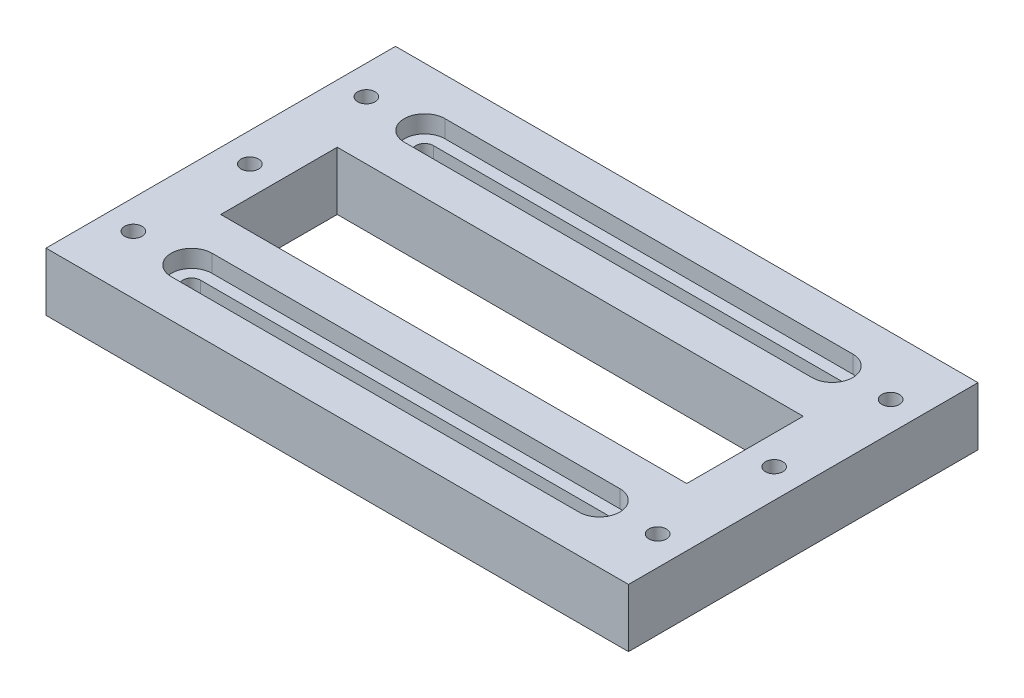
SolidWorks part; units mm, degrees
ref_plane "Front Plane" through (0, 0, 0) normal (0, 0, 1) x (1, 0, 0)
ref_plane "Top Plane" through (0, 0, 0) normal (0, 1, 0) x (1, 0, 0)
ref_plane "Right Plane" through (0, 0, 0) normal (1, 0, 0) x (0, 0, -1)
sketch "Sketch1" plane through (0, 0, 0) normal (0, 1, 0) x (1, 0, 0)
  line L0 (10, 40) -> (10, 20)
  line L1 (0, 0) -> (100, 0)
  line L2 (0, 0) -> (0, 60)
  line L3 (0, 60) -> (100, 60)
  line L4 (100, 0) -> (100, 60)
  line L5 (10, 20) -> (90, 20)
  line L6 (90, 20) -> (90, 40)
  line L7 (90, 40) -> (10, 40)
  line L8 (85, 51.5) -> (15, 51.5)
  line L9 (85, 48.5) -> (15, 48.5)
  line L10 (85, 8.5) -> (15, 8.5)
  line L11 (85, 11.5) -> (15, 11.5)
  circle A2 centre (5, 30) radius 1.5
  circle A7 centre (5, 50) radius 1.5
  circle A29 centre (5, 10) radius 1.5
  circle A30 centre (15, 50) radius 1.5
  circle A31 centre (15, 10) radius 1.5
  circle A44 centre (85, 50) radius 1.5
  circle A45 centre (85, 10) radius 1.5
  circle A46 centre (95, 50) radius 1.5
  circle A47 centre (95, 10) radius 1.5
  circle A48 centre (95, 30) radius 1.5
  point P29 (0, 0)
  dimension "D7" = 3
  dimension "D25" = 3
  dimension "D4" = 3
  dimension "D10" = 3
  dimension "D18" = 3
  dimension "D19" = 3
  dimension "D20" = 3
  dimension "D21" = 3
  dimension "D1" = 60
  dimension "D2" = 100
  dimension "D3" = 10
  dimension "D14" = 5
  dimension "D15" = 30
  dimension "D22" = 20
  dimension "D23" = 20
  dimension "D24" = 10
  dimension "D28" = 10
  dimension "D5" = 10
  dimension "D6" = 5
  dimension "D8" = 5
  dimension "D11" = 5
  dimension "D12" = 30
  dimension "D9" = 10
  dimension "D13" = 5
  dimension "D16" = 5
  dimension "D17" = 10
  dimension "D26" = 10
  dimension "D27" = 10
extrude "Boss-Extrude1" add sketch "Sketch1" along normal blind 10 contours L1 L4 L3 L2 A48 A47 A46 A45 A44 L9 A30 L8 A31 A29 A7 A2 L7 L6 L5 L0 region at (1.1662, 0, -30)
sketch "Sketch3" plane through (0, 10, 0) normal (0, 1, 0) x (1, 0, 0)
  line L9 (15, 46.5) -> (85, 46.5)
  line L10 (85, 53.5) -> (15, 53.5)
  line L11 (15, 46.5) -> (85, 46.5)
  line L12 (85, 53.5) -> (15, 53.5)
  line L22 (15, 6.5) -> (85, 6.5)
  line L23 (85, 13.5) -> (15, 13.5)
  line L24 (15, 6.5) -> (85, 6.5)
  line L25 (85, 13.5) -> (15, 13.5)
  arc A5 (85, 46.5) -> (85, 53.5) centre (85, 50) ccw
  arc A6 (15, 53.5) -> (15, 46.5) centre (15, 50) ccw
  arc A7 (85, 46.5) -> (85, 53.5) centre (85, 50) ccw
  arc A8 (15, 53.5) -> (15, 46.5) centre (15, 50) ccw
  arc A14 (85, 6.5) -> (85, 13.5) centre (85, 10) ccw
  arc A15 (15, 13.5) -> (15, 6.5) centre (15, 10) ccw
  arc A16 (85, 6.5) -> (85, 13.5) centre (85, 10) ccw
  arc A17 (15, 13.5) -> (15, 6.5) centre (15, 10) ccw
  dimension "D1" = 2
  dimension "D2" = 2
extrude "Cut-Extrude2" cut sketch "Sketch3" against normal blind 3
equation "\"boltdiameter\"=3"
equation "\"D25@Sketch1\"=\"boltdiameter\""
equation "\"D4@Sketch1\"=\"boltdiameter\""
equation "\"D10@Sketch1\"=\"boltdiameter\""
equation "\"D7@Sketch1\"=\"boltdiameter\""
equation "\"D18@Sketch1\"=\"boltdiameter\""
equation "\"D19@Sketch1\"=\"boltdiameter\""
equation "\"boltfacediameter\"=7"
equation "\"D20@Sketch1\"=\"boltdiameter\""
equation "\"D21@Sketch1\"=\"boltdiameter\""
equation "\"boltfacediam\"=2"
equation "\"D1@Sketch3\"=\"boltfacediam\""
equation "\"D2@Sketch3\"=\"boltfacediam\""
